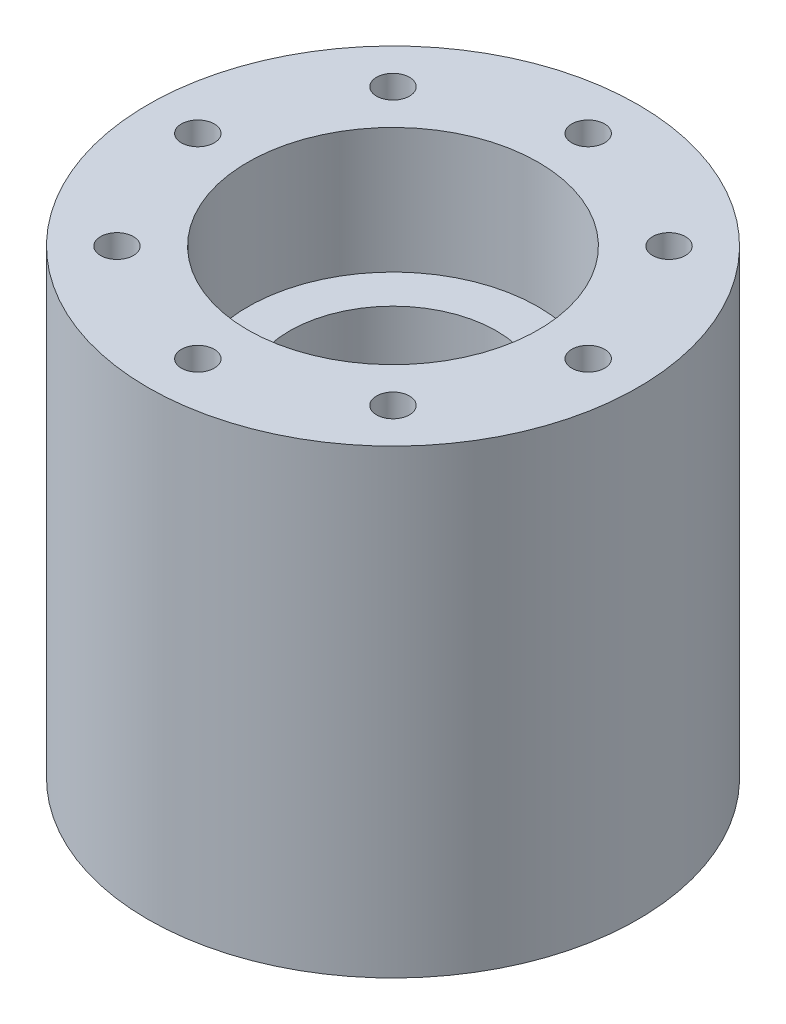
SolidWorks part; units mm, degrees
ref_plane "Top Plane" through (0, 0, 0) normal (0, 0, 1) x (1, 0, 0)
ref_plane "Front Plane" through (0, 0, 0) normal (0, 1, 0) x (1, 0, 0)
ref_plane "Right Plane" through (0, 0, 0) normal (1, 0, 0) x (0, 0, -1)
sketch "Body Sketch" plane through (0, 0, 0) normal (0, 1, 0) x (1, 0, 0)
  circle A0 centre (0, 0) radius 18.6375
  dimension "D1" = 37.275
extrude "Body Extrude" add sketch "Body Sketch" along normal blind 35.0312
sketch "Bearing Pocket Sketch" plane through (0, 0, 0) normal (0, -1, 0) x (-1, 0, 0)
  circle A0 centre (0, 0) radius 11.049
  dimension "D1" = 22.098
extrude "Bearing Pocket Cut 1" cut sketch "Bearing Pocket Sketch" against normal blind 9.525
extrude "Bearing Pocket Cut 2" cut sketch "Bearing Pocket Sketch<2>" along normal blind 9.525 from surface starting at face at (0, 35.0312, 18.6375)
sketch "Bearing Pocket Sketch<2>" plane through (0, 0, 0) normal (0, -1, 0) x (-1, 0, 0) same geometry as "Bearing Pocket Sketch"
sketch "Bore Sketch" plane through (0, 0, 0) normal (0, -1, 0) x (-1, 0, 0)
  circle A0 centre (0, 0) radius 7.874
  circle A1 centre (0, 0) radius 11.049 construction
  circle A2 centre (0, 0) radius 11.049
  dimension "D1" = 3.175
extrude "Bore Cut" cut sketch "Bore Sketch" against normal through all contours A0
sketch "Mounting Hole Sketch 1"
  circle A1 centre (0, 0) radius 11.049 construction
  point P0 (0, -14.8433)
  point P5 (10.4958, -10.4958)
  point P6 (14.8433, 0)
  point P7 (10.4958, 10.4958)
  point P8 (0, 14.8433)
  point P9 (-10.4958, 10.4958)
  point P10 (-14.8433, 0)
  point P11 (-10.4958, -10.4958)
  point P12 (0, 0)
  dimension "D1" = 14.8433
  dimension "D2" = 8
hole_wizard "M3x0.5 Tapped Hole1" positions "3DSketch3" profile "Sketch8" tap size "M3x0.5" standard "ANSI Metric"
sketch3d "3DSketch3"
  point P0 (0, 0, 14.8433)
  point P3 (10.4958, 0, 10.4958)
  point P6 (14.8433, 0, 0)
  point P9 (10.4958, 0, -10.4958)
  point P12 (0, 0, -14.8433)
  point P15 (-10.4958, 0, -10.4958)
  point P18 (-14.8433, 0, 0)
  point P21 (-10.4958, 0, 10.4958)
sketch "Sketch8" plane through (0, 0, 14.8433) normal (1, 0, 0) x (0, 0, -1)
  line L0 (0, 0) -> (0, 8.2517)
  line L1 (0, 8.2517) -> (1.25, 7.5006)
  line L2 (1.25, 7.5006) -> (1.25, 0)
  line L5 (1.25, 0) -> (0, 0)
  line L10 (0, 8.2517) -> (-1.25, 7.5006) construction
  line L11 (0, -6.35) -> (0, 107.95) construction
  dimension "Tap Drill Dia." = 2.5
  dimension "Tap Drill Depth" = 7.5006
  dimension "Drill Angle" = 118
cosmetic thread "Hole Thread3" parameters "D1"=5.9995, "D2"=3
cosmetic thread "Hole Thread4" parameters "D1"=5.9995, "D2"=3
cosmetic thread "Hole Thread5" parameters "D1"=5.9995, "D2"=3
cosmetic thread "Hole Thread6" parameters "D1"=5.9995, "D2"=3
cosmetic thread "Hole Thread7" parameters "D1"=5.9995, "D2"=3
cosmetic thread "Hole Thread8" parameters "D1"=5.9995, "D2"=3
cosmetic thread "Hole Thread9" parameters "D1"=5.9995, "D2"=3
cosmetic thread "Hole Thread10" parameters "D1"=5.9995, "D2"=3
sketch "Mounting Hole Sketch 2" plane through (0, 35.0312, 0) normal (0, 1, 0) x (1, 0, 0)
  point P0 (0, -14.8433)
  point P5 (-10.4958, -10.4958)
  point P6 (-14.8433, 0)
  point P7 (-10.4958, 10.4958)
  point P8 (0, 14.8433)
  point P9 (10.4958, 10.4958)
  point P10 (14.8433, 0)
  point P11 (10.4958, -10.4958)
  point P12 (0, 0)
  dimension "D1" = 14.8433
  dimension "D2" = 8
hole_wizard "M3x0.5 Tapped Hole3" positions "3DSketch4" profile "Sketch13" tap size "M3x0.5" standard "ANSI Metric"
sketch3d "3DSketch4"
  point P0 (0, 35.0312, 14.8433)
  point P3 (10.4958, 35.0312, 10.4958)
  point P6 (14.8433, 35.0312, 0)
  point P9 (10.4958, 35.0312, -10.4958)
  point P12 (0, 35.0312, -14.8433)
  point P15 (-10.4958, 35.0312, -10.4958)
  point P18 (-14.8433, 35.0312, 0)
  point P21 (-10.4958, 35.0312, 10.4958)
sketch "Sketch13" plane through (0, 35.0312, 14.8433) normal (1, 0, 0) x (0, 0, 1)
  line L0 (0, 0) -> (0, 8.2517)
  line L1 (0, 8.2517) -> (1.25, 7.5006)
  line L2 (1.25, 7.5006) -> (1.25, 0)
  line L5 (1.25, 0) -> (0, 0)
  line L10 (0, 8.2517) -> (-1.25, 7.5006) construction
  line L11 (0, -6.35) -> (0, 107.95) construction
  dimension "Tap Drill Dia." = 2.5
  dimension "Tap Drill Depth" = 7.5006
  dimension "Drill Angle" = 118
cosmetic thread "Hole Thread27" parameters "D1"=5.9995, "D2"=3
cosmetic thread "Hole Thread28" parameters "D1"=5.9995, "D2"=3
cosmetic thread "Hole Thread29" parameters "D1"=5.9995, "D2"=3
cosmetic thread "Hole Thread30" parameters "D1"=5.9995, "D2"=3
cosmetic thread "Hole Thread31" parameters "D1"=5.9995, "D2"=3
cosmetic thread "Hole Thread32" parameters "D1"=5.9995, "D2"=3
cosmetic thread "Hole Thread33" parameters "D1"=5.9995, "D2"=3
cosmetic thread "Hole Thread34" parameters "D1"=5.9995, "D2"=3
equation "\"turing_spool_bearingpocket\"=0.87"
equation "\"D1@Bearing Pocket Sketch\"=\"turing_spool_bearingpocket\""
equation "\"turing_spool_holeradius\"=0.58438"
equation "\"D1@Mounting Hole Sketch 1\"=\"turing_spool_holeradius\""
equation "\"D1@Mounting Hole Sketch 2\"=\"turing_spool_holeradius\""
